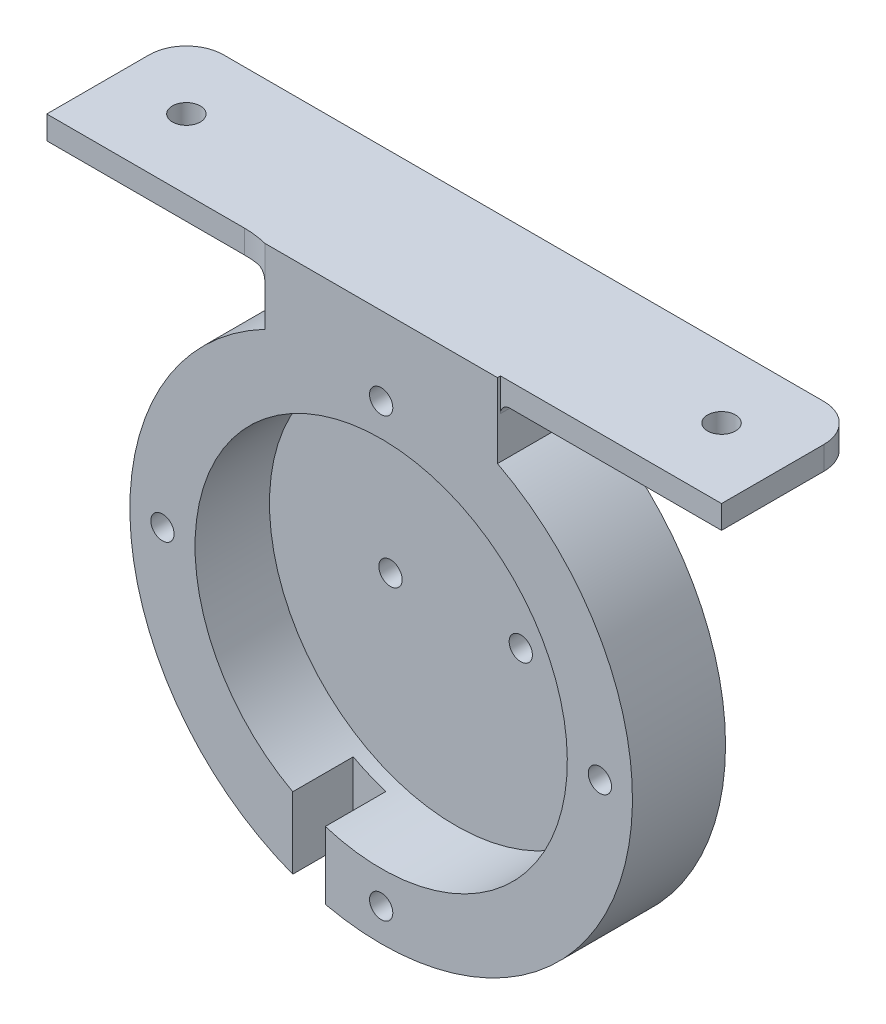
SolidWorks part; units mm, degrees
ref_plane "Front Plane" through (0, 0, 0) normal (0, 0, 1) x (1, 0, 0)
ref_plane "Top Plane" through (0, 0, 0) normal (0, 1, 0) x (1, 0, 0)
ref_plane "Right Plane" through (0, 0, 0) normal (1, 0, 0) x (0, 0, -1)
sketch "Sketch1" plane through (0, 0, 0) normal (0, 0, 1) x (1, 0, 0)
  circle A0 centre (0, 0) radius 27
  circle A1 centre (0, 0) radius 23.5 construction
  circle A2 centre (0, 23.5) radius 1.25
  circle A3 centre (23.5, 0) radius 1.25
  circle A4 centre (0, -23.5) radius 1.25
  circle A5 centre (-23.5, 0) radius 1.25
  circle A6 centre (0, 0) radius 20
  point P15 (0, 0)
  dimension "D1" = 54
  dimension "D2" = 47
  dimension "D3" = 2.5
  dimension "D5" = 40
  dimension "D4" = 4
extrude "Boss-Extrude1" add sketch "Sketch1" along normal blind 10
sketch "Sketch3" plane through (0, 0, 0) normal (0, 0, 1) x (1, 0, 0)
  circle A0 centre (0, 0) radius 20
  circle A1 centre (0, 0) radius 7 construction
  circle A2 centre (-7, 0) radius 1.25
  circle A3 centre (7, 0) radius 1.25
  circle A4 centre (0, 0) radius 11.5 construction
  dimension "D1" = 40
  dimension "D2" = 14
  dimension "D3" = 2.5
  dimension "D4" = 23
extrude "Boss-Extrude2" add sketch "Sketch3" along normal blind 2
sketch "Sketch5" plane through (0, 0, 10) normal (0, 0, 1) x (1, 0, 0)
  line L0 (0, -5.5) -> (0, 5.5) construction
  line L1 (-12.5, 23.9322) -> (-4.2519, 23.9322)
  line L2 (-12.5, 23.9322) -> (-12.5, 31.9322)
  line L3 (-12.5, 31.9322) -> (12.5, 31.9322)
  line L4 (12.5, 23.9322) -> (12.5, 31.9322)
  line L5 (4.2678, 23.9322) -> (0, 26.2545)
  line L6 (0, 26.2545) -> (-4.2519, 23.9322)
  line L7 (4.2678, 23.9322) -> (12.5, 23.9322)
  circle A0 centre (0, 0) radius 27 construction
  dimension "D1" = 12.5
  dimension "D2" = 25
  dimension "D3" = 8
extrude "Boss-Extrude3" add sketch "Sketch5" against normal blind 6
sketch "Sketch4" plane through (0, 0, 0) normal (0, 1, 0) x (1, 0, 0)
  line L1 (-9.5, -3.5) -> (-6, -3.5)
  line L2 (-9.5, -3.5) -> (-9.5, -12.8373)
  line L3 (-9.5, -12.8373) -> (-6, -12.8373)
  line L4 (-6, -3.5) -> (-6, -12.8373)
  line L5 (-29.7, 0) -> (29.7, 0) construction
  point P6 (-12, -7.5)
  dimension "D1" = 3.5
  dimension "D2" = 3.5
  dimension "D4" = 6
extrude "Cut-Extrude1" cut sketch "Sketch4" against normal up to surface (26.3249 mm away) up to face at (0, 11.9661, 7)
sketch "Sketch6" plane through (0, 31.9322, 0) normal (0, 1, 0) x (1, 0, 0)
  line L0 (12.5, -4) -> (12.5, -10) construction
  line L1 (-12.5, -10) -> (12.5, -10)
  line L2 (-12.5, -10) -> (-12.5, 5.32)
  line L3 (-12.5, 5.32) -> (12.5, 5.32)
  line L4 (12.5, -10) -> (12.5, 5.32)
  dimension "D1" = 15.32
extrude "Boss-Extrude4" add sketch "Sketch6" against normal blind 2.5
sketch "Sketch7" plane through (0, 31.9322, 0) normal (0, 1, 0) x (1, 0, 0)
  line L0 (0, -5.5) -> (0, 5.5) construction
  line L1 (-36.25, -67.18) -> (36.25, -67.18) construction
  line L2 (-36.25, -67.18) -> (-36.25, 1.32) construction
  line L3 (-32.25, 5.32) -> (32.25, 5.32) construction
  line L4 (36.25, -67.18) -> (36.25, 1.32) construction
  line L5 (-28.75, -9.68) -> (-36.25, -9.68)
  line L6 (0, 5.32) -> (-36.25, 5.32)
  line L7 (-36.25, -9.68) -> (-36.25, -2.18)
  line L8 (12.5, -4) -> (-12.5, -4) construction
  line L9 (0, 5.32) -> (0, -9.68)
  line L10 (0, -9.68) -> (-28.75, -9.68)
  line L11 (-36.25, 5.32) -> (-36.25, -2.18)
  arc A0 (32.25, 5.32) -> (36.25, 1.32) centre (32.25, 1.32) cw construction
  arc A1 (-36.25, 1.32) -> (-32.25, 5.32) centre (-32.25, 1.32) cw
  circle A3 centre (-28.75, -2.18) radius 1.5
  point P4 (0, 5.32)
  point P11 (36.25, 5.32)
  point P14 (-36.25, 5.32)
  point P21 (-36.25, -9.68)
  dimension "D4" = 4
  dimension "D7" = 3
  dimension "D1" = 72.5
  dimension "D2" = 72.5
  dimension "D3" = 9.32
  dimension "D5" = 15
extrude "Boss-Extrude5" add sketch "Sketch7" against normal blind 2.5 contours L10 L9 L6 A1 L11 A3 region at (-17.8732, 31.9322, 2.2225)
fillet "Fillet2" radius 10 1 edges at (-12.5, 30.6822, 9.68)
sketch "Sketch8" plane through (0, 31.9322, 0) normal (0, 1, 0) x (1, 0, 0)
  circle A0 centre (-28.75, -2.18) radius 2.5
  circle A1 centre (-28.75, -2.18) radius 4
  dimension "D1" = 5
  dimension "D2" = 8
extrude "Boss-Extrude6" [suppressed] add sketch "Sketch8" against normal blind 5
mirror "Mirror1" about plane through (0, 0, 0) normal (1, 0, 0) of "Boss-Extrude4", "Boss-Extrude5", "Boss-Extrude6"
fillet "Fillet3" radius 1 3 edges at (0, 29.4322, 4) (12.5, 29.4322, 6.84) (-12.5, 29.4322, 7)
fillet "Fillet4" [suppressed] radius 10
